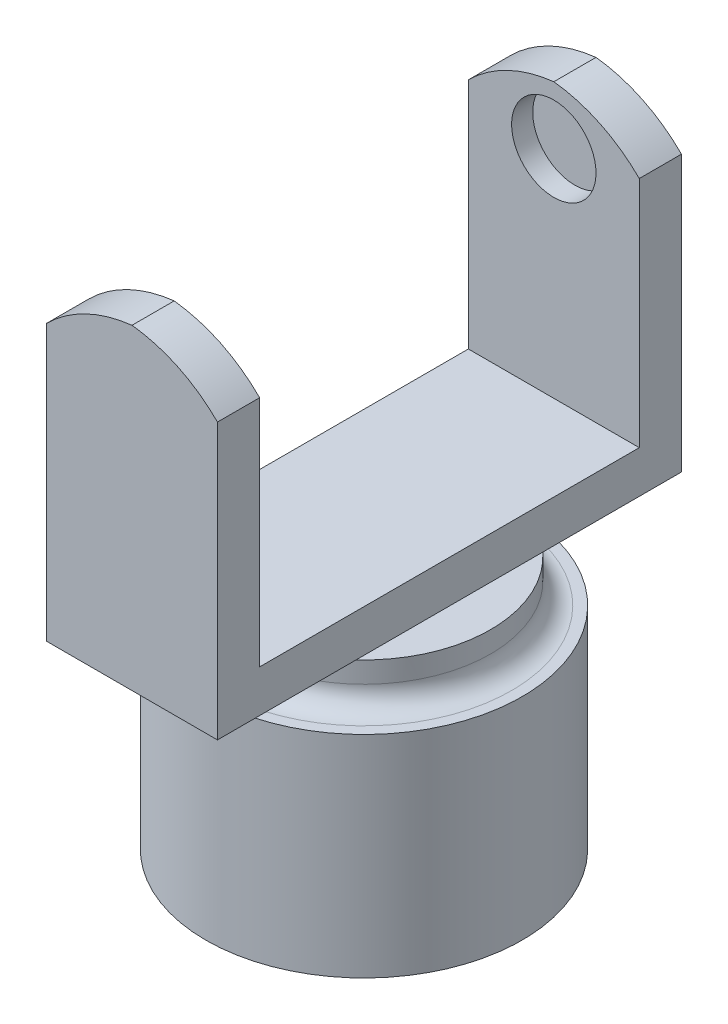
SolidWorks part; units mm, degrees
ref_plane "Front Plane" through (0, 0, 0) normal (0, 0, 1) x (1, 0, 0)
ref_plane "Top Plane" through (0, 0, 0) normal (0, 1, 0) x (1, 0, 0)
ref_plane "Right Plane" through (0, 0, 0) normal (1, 0, 0) x (0, 0, -1)
sketch "Sketch1" plane through (0, 0, 0) normal (0, 1, 0) x (1, 0, 0)
  circle A0 centre (0, 0) radius 7.5
  dimension "D1" = 15
extrude "Boss-Extrude1" add sketch "Sketch1" along normal blind 10
sketch "Sketch5" plane through (0, 10, 0) normal (0, 1, 0) x (1, 0, 0)
  circle A0 centre (0, 0) radius 6
  dimension "D1" = 12
extrude "Boss-Extrude2" add sketch "Sketch5" along normal blind 2
fillet "Fillet2" radius 1 1 edges at (0, 10, 6)
sketch "Sketch6" plane through (0, 0, 0) normal (1, 0, 0) x (0, 0, -1)
  line L0 (6, 12) -> (-6, 12) construction
  line L1 (6, 12) -> (-6, 12)
  line L2 (6, 12) -> (11, 12)
  line L3 (11, 12) -> (11, 27)
  line L4 (11, 27) -> (9, 27)
  line L5 (9, 27) -> (9, 14)
  line L6 (9, 14) -> (-9, 14)
  line L7 (-9, 14) -> (-9, 27)
  line L8 (-9, 27) -> (-11, 27)
  line L9 (-11, 27) -> (-11, 12)
  line L10 (-11, 12) -> (-6, 12)
  dimension "D1" = 15
  dimension "D2" = 2
  dimension "D3" = 13
  dimension "D4" = 5
extrude "Boss-Extrude3" add sketch "Sketch6" along normal blind 6 and the other way blind 6
sketch "Sketch9" plane through (0, 0, 11) normal (0, 0, 1) x (1, 0, 0)
  line L0 (0, 27) -> (0, 12) construction
  line L4 (-6, 12) -> (6, 12)
  line L5 (6, 12) -> (6, 27)
  line L6 (6, 27) -> (-6, 27)
  line L7 (-6, 27) -> (-6, 12)
  line L8 (-6, 12) -> (6, 12)
  line L9 (6, 12) -> (6, 27)
  line L10 (6, 27) -> (-6, 27)
  line L11 (-6, 27) -> (-6, 12)
  arc A0 (0, 27) -> (-6, 19.5) centre (0.75, 20.25) ccw
  arc A1 (0, 27) -> (6, 19.5) centre (-0.75, 20.25) cw
  line M7 (6, 12) -> (6, 27)
  line M8 (6, 27) -> (-6, 27)
  line M9 (-6, 27) -> (-6, 12)
  dimension "D1" = 0
extrude "Cut-Extrude4" cut sketch "Sketch9" against normal blind 29 contours A0 L10 M9 | A1 M8 M7 region at (-4.5286, 25.5286, 11) region at (4.5286, 25.5286, 11)
sketch "Sketch10" plane through (0, 0, 9) normal (0, 0, -1) x (-1, 0, 0)
  line L0 (6, 14) -> (6, 21) construction
  circle A0 centre (0, 24.25) radius 2
  arc A1 (6, 21) -> (0, 27) centre (-0.75, 20.25) ccw construction
  dimension "D1" = 4
  dimension "D2" = 4
  dimension "D3" = 6
extrude "Cut-Extrude5" cut sketch "Sketch10" against normal blind 1 and the other way blind 19
sketch "Sketch12" plane through (0, 0, 0) normal (0, -1, 0) x (1, 0, 0)
  circle A0 centre (0, 0) radius 5
  dimension "D1" = 10
extrude "Cut-Extrude6" cut sketch "Sketch12" against normal blind 7
sketch "Sketch13" plane through (0, 0, -11) normal (0, 0, -1) x (-1, 0, 0)
  line L0 (-4.0523, 25.0523) -> (-4.0523, 12)
  line L1 (4.0523, 25.0523) -> (4.0523, 12)
  line L3 (-6, 21) -> (-6, 12)
  line L4 (-6, 12) -> (6, 12)
  line L5 (6, 12) -> (6, 21)
  line L6 (-6, 21) -> (-6, 12)
  line L7 (-6, 12) -> (6, 12)
  line L8 (6, 12) -> (6, 21)
  arc A2 (0, 27) -> (-6, 21) centre (0.75, 20.25) ccw
  arc A3 (6, 21) -> (0, 27) centre (-0.75, 20.25) ccw
  arc A4 (0, 27) -> (-6, 21) centre (0.75, 20.25) ccw
  arc A5 (6, 21) -> (0, 27) centre (-0.75, 20.25) ccw
  arc M6 (0, 27) -> (-6, 21) centre (0.75, 20.25) ccw
  line M7 (-6, 21) -> (-6, 12)
  line M8 (-6, 12) -> (6, 12)
  line M9 (6, 12) -> (6, 21)
  arc M10 (6, 21) -> (0, 27) centre (-0.75, 20.25) ccw
  dimension "D1" = 0
extrude "Cut-Extrude7" cut sketch "Sketch13" against normal blind 36 contours L0 M6 M7 M8 | L1 M10 M8 M9 region at (4.9766, 17.8566, -11) region at (-4.9766, 17.8566, -11)
